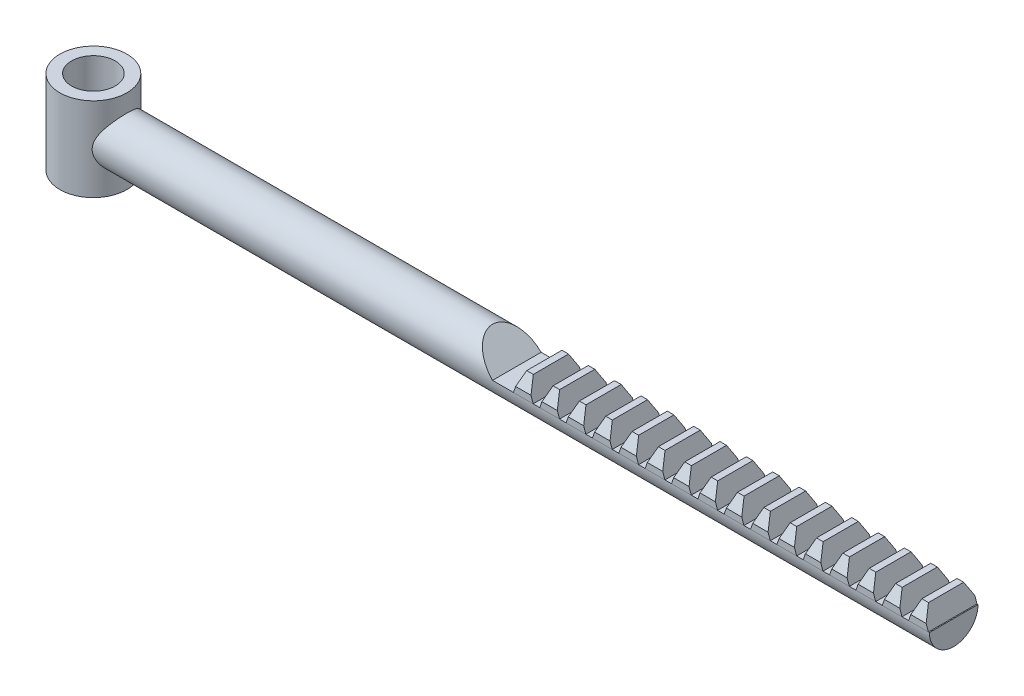
SolidWorks part; units mm, degrees
ref_plane "前视基准面" through (0, 0, 0) normal (0, 0, 1) x (1, 0, 0)
ref_plane "上视基准面" through (0, 0, 0) normal (0, 1, 0) x (1, 0, 0)
ref_plane "右视基准面" through (0, 0, 0) normal (1, 0, 0) x (0, 0, -1)
other "Configuration Table"
sketch "草图1" plane through (0, 0, 0) normal (0, 1, 0) x (1, 0, 0)
  circle A0 centre (0, 0) radius 2.6
  circle A1 centre (0, 0) radius 4
  dimension "D1" = 5.2
  dimension "D2" = 8
extrude "凸台-拉伸1" add sketch "草图1" along normal blind 10
ref_plane "基准面1" through (2.6, 0, 0) normal (-1, 0, 0) x (0, 0, 1)
sketch "草图3" plane through (2.6, 0, 0) normal (-1, 0, 0) x (0, 0, 1)
  line L0 (0, -1000) -> (0, 49000) construction
  line L1 (-4, 0) -> (4, 0) construction
  line L2 (-1004, 5) -> (48996, 5) construction
  line L3 (-4, 10) -> (-4, 0) construction
  circle A0 centre (0, 5) radius 2.9
  point P7 (0, 0)
  point P12 (-4, 5)
  dimension "D1" = 5.8
extrude "凸台-拉伸2" add sketch "草图3" against normal blind 100
sketch "草图4" plane through (0, 10, 0) normal (0, 1, 0) x (1, 0, 0)
  line L1 (47.6, -2.9) -> (102.6, -2.9)
  line L2 (47.6, -2.9) -> (47.6, 2.9)
  line L3 (47.6, 2.9) -> (102.6, 2.9)
  line L4 (102.6, -2.9) -> (102.6, 2.9)
  line L5 (47.6, -2.9) -> (102.6, 2.9) construction
  line L6 (47.6, 2.9) -> (102.6, -2.9) construction
  point P0 (75.1, 0)
  dimension "D1" = 55
  dimension "D2" = 5.8
extrude "切除-拉伸1" cut sketch "草图4" against normal blind 5
sketch "草图5" plane through (0, 0, 0) normal (0, 0, 1) x (1, 0, 0)
  line L0 (47.6, 5) -> (102.6, 5) construction
  line L1 (52.9928, 5) -> (55.3493, 5)
  line L2 (71.0593, 5) -> (70.2738, 7.25)
  line L3 (70.2738, 7.25) -> (69.4883, 7.25)
  line L4 (69.4883, 7.25) -> (68.7028, 5)
  line L5 (56.1348, 5) -> (58.4912, 5)
  line L6 (67.9173, 5) -> (67.1318, 7.25)
  line L7 (67.1318, 7.25) -> (66.3463, 7.25)
  line L8 (66.3463, 7.25) -> (65.5608, 5)
  line L9 (59.2767, 5) -> (61.6332, 5)
  line L10 (64.7753, 5) -> (63.9898, 7.25)
  line L11 (63.9898, 7.25) -> (63.2043, 7.25)
  line L12 (63.2043, 7.25) -> (62.4188, 5)
  line L13 (62.4188, 5) -> (64.7753, 5)
  line L14 (61.6332, 5) -> (60.8477, 7.25)
  line L15 (60.8477, 7.25) -> (60.0623, 7.25)
  line L16 (60.0623, 7.25) -> (59.2767, 5)
  line L17 (65.5608, 5) -> (67.9173, 5)
  line L18 (58.4912, 5) -> (57.7058, 7.25)
  line L19 (57.7058, 7.25) -> (56.9203, 7.25)
  line L20 (56.9203, 7.25) -> (56.1348, 5)
  line L21 (68.7028, 5) -> (71.0593, 5)
  line L22 (55.3493, 5) -> (54.5638, 7.25)
  line L23 (54.5638, 7.25) -> (53.7783, 7.25)
  line L24 (53.7783, 7.25) -> (52.9928, 5)
  line L25 (71.8448, 5) -> (74.2013, 5)
  line L27 (47.6, 5) -> (47.6, 7.9) construction
  line L29 (74.9868, 5) -> (77.3433, 5)
  line L30 (89.9113, 5) -> (89.1258, 7.25)
  line L31 (89.1258, 7.25) -> (88.3403, 7.25)
  line L32 (88.3403, 7.25) -> (87.5548, 5)
  line L33 (78.1288, 5) -> (80.4853, 5)
  line L34 (86.7693, 5) -> (85.9838, 7.25)
  line L35 (85.9838, 7.25) -> (85.1983, 7.25)
  line L36 (85.1983, 7.25) -> (84.4128, 5)
  line L37 (81.2708, 5) -> (83.6273, 5)
  line L38 (83.6273, 5) -> (82.8418, 7.25)
  line L39 (82.8418, 7.25) -> (82.0563, 7.25)
  line L40 (82.0563, 7.25) -> (81.2708, 5)
  line L41 (84.4128, 5) -> (86.7693, 5)
  line L42 (80.4853, 5) -> (79.6998, 7.25)
  line L43 (79.6998, 7.25) -> (78.9143, 7.25)
  line L44 (78.9143, 7.25) -> (78.1288, 5)
  line L45 (87.5548, 5) -> (89.9113, 5)
  line L46 (77.3433, 5) -> (76.5578, 7.25)
  line L47 (76.5578, 7.25) -> (75.7723, 7.25)
  line L48 (75.7723, 7.25) -> (74.9868, 5)
  line L49 (90.6968, 5) -> (93.0533, 5)
  line L50 (74.2013, 5) -> (73.4158, 7.25)
  line L51 (73.4158, 7.25) -> (72.6303, 7.25)
  line L52 (72.6303, 7.25) -> (71.8448, 5)
  line L53 (93.8388, 5) -> (96.1953, 5)
  line L54 (47.6, 5) -> (47.6, 7.9)
  line L55 (96.9808, 5) -> (99.3373, 5)
  line L56 (100.1228, 5) -> (102.4793, 5)
  line L57 (50.5, 5) -> (47.6, 7.9)
  line L58 (47.6, 5) -> (50.5, 5)
  line L62 (102.4793, 5) -> (101.6938, 7.25)
  line L63 (101.6938, 7.25) -> (100.9083, 7.25)
  line L64 (100.9083, 7.25) -> (100.1228, 5)
  line L66 (99.3373, 5) -> (98.5518, 7.25)
  line L67 (98.5518, 7.25) -> (97.7663, 7.25)
  line L68 (97.7663, 7.25) -> (96.9808, 5)
  line L70 (96.1953, 5) -> (95.4098, 7.25)
  line L71 (95.4098, 7.25) -> (94.6243, 7.25)
  line L72 (94.6243, 7.25) -> (93.8388, 5)
  line L74 (93.0533, 5) -> (92.2678, 7.25)
  line L75 (92.2678, 7.25) -> (91.4823, 7.25)
  line L76 (91.4823, 7.25) -> (90.6968, 5)
extrude "凸台-拉伸3" add sketch "草图5" along normal blind 2.9 and the other way blind 2.9
sketch "草图6" plane through (47.6, 0, 0) normal (-1, 0, 0) x (0, 0, 1)
  line L2 (-2.9, 7.9) -> (-2.9, 5)
  line L3 (0, 7.9) -> (-2.9, 7.9)
  line L4 (-2.9, 7.9) -> (-2.9, 5)
  line L5 (0, 7.9) -> (-2.9, 7.9)
  line L6 (2.9, 7.9) -> (0, 7.9)
  line L7 (2.9, 5) -> (2.9, 7.9)
  line L8 (2.9, 7.9) -> (0, 7.9)
  line L9 (2.9, 5) -> (2.9, 7.9)
  arc A1 (0, 7.9) -> (-2.9, 5) centre (0, 5) ccw
  arc A2 (0, 7.9) -> (-2.9, 5) centre (0, 5) ccw
  arc A3 (2.9, 5) -> (0, 7.9) centre (0, 5) ccw
  arc A4 (2.9, 5) -> (0, 7.9) centre (0, 5) ccw
  line M7 (-2.9, 7.9) -> (-2.9, 5)
  arc M8 (-2.9, 5) -> (0, 7.9) centre (0, 5) cw
  line M9 (0, 7.9) -> (-2.9, 7.9)
  dimension "D1" = 0
  dimension "D2" = 0
extrude "切除-拉伸2" cut sketch "草图6" against normal up to next contours M9 M7 M8 | A4 L9 L8 region at (47.6, 7.2522, -2.2522) region at (47.6, 7.2522, 2.2522)
sketch "草图7" plane through (102.6, 0, 0) normal (1, 0, 0) x (0, 0, -1)
  line L0 (2.9, 5.75) -> (2.1, 7.25)
  line L1 (-2.9, 5.75) -> (-2.1, 7.25)
  line L2 (-2.1, 7.25) -> (-2.9, 7.25)
  line L4 (2.9, 7.25) -> (-2.9, 7.25)
  line L5 (-2.9, 7.25) -> (-2.9, 5)
  line L6 (-2.9, 5) -> (2.9, 5)
  line L7 (2.9, 5) -> (2.9, 7.25)
  line L8 (2.9, 7.25) -> (2.1, 7.25)
  line L9 (-2.9, 7.25) -> (-2.9, 5.75)
  line L11 (2.9, 5.75) -> (2.9, 7.25)
  dimension "D2" = 1.5
  dimension "D3" = 0.8
  dimension "D4" = 0.8
  dimension "D5" = 1.5
  dimension "D1" = 0
extrude "切除-拉伸3" cut sketch "草图7" against normal up to surface (54.35 mm away) up to face at (49.05, 6.45, 0)
